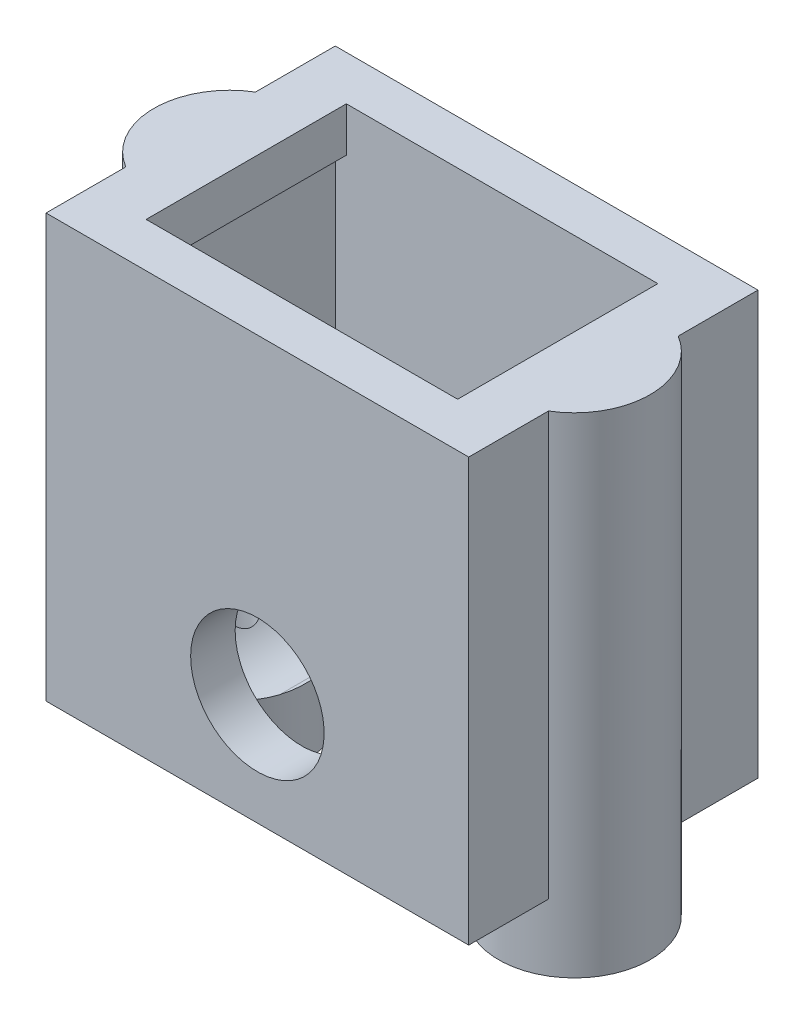
SolidWorks part; units mm, degrees
ref_plane "Plano frontal" through (0, 0, 0) normal (0, 0, 1) x (1, 0, 0)
ref_plane "Plano superior" through (0, 0, 0) normal (0, 1, 0) x (1, 0, 0)
ref_plane "Plano direito" through (0, 0, 0) normal (1, 0, 0) x (0, 0, -1)
sketch "Esboço1" plane through (0, 0, 0) normal (0, 1, 0) x (1, 0, 0)
  line L1 (-7.5, -4.5) -> (7.5, -4.5)
  line L2 (-7.5, -4.5) -> (-7.5, 4.5)
  line L3 (-7.5, 4.5) -> (7.5, 4.5)
  line L4 (7.5, -4.5) -> (7.5, 4.5)
  line L5 (-7.5, -4.5) -> (7.5, 4.5) construction
  line L6 (-7.5, 4.5) -> (7.5, -4.5) construction
  line L7 (-9.5, -6.5) -> (9.5, -6.5)
  line L8 (-9.5, -6.5) -> (-9.5, 6.5)
  line L9 (-9.5, 6.5) -> (9.5, 6.5)
  line L10 (9.5, -6.5) -> (9.5, 6.5)
  line L11 (-9.5, -6.5) -> (9.5, 6.5) construction
  line L12 (-9.5, 6.5) -> (9.5, -6.5) construction
  point P0 (0, 0)
  point P6 (0, 0)
  dimension "D1" = 15
  dimension "D2" = 9
  dimension "D3" = 2
  dimension "D4" = 2
extrude "Ressalto-extrusão1" add sketch "Esboço1" along normal blind 17
sketch "Esboço2" plane through (0, 0, 0) normal (0, -1, 0) x (1, 0, 0)
  line L0 (7.75, 0) -> (-7.75, 0) construction
  circle A0 centre (7.75, 0) radius 3.4
  circle A1 centre (-7.75, 0) radius 3.4
  circle A2 centre (-7.75, 0) radius 1
  circle A3 centre (7.75, 0) radius 1
  point P4 (0, 0)
  dimension "D2" = 6.8
  dimension "D3" = 6.8
  dimension "D4" = 2
  dimension "D5" = 2
  dimension "D1" = 15.5
extrude "Ressalto-extrusão2" add sketch "Esboço2" along normal blind 3
fillet "Filete1" radius 3 4 edges at (-7.5, 0, 2.1795) (-7.5, 0, -2.1795) (7.5, 0, -2.1795) (7.5, 0, 2.1795)
sketch "Esboço3" plane through (0, 0, 0) normal (0, 1, 0) x (1, 0, 0)
  line L1 (-9.5, -2.915) -> (-9.5, 2.915)
  line L2 (-9.5, -2.915) -> (-9.5, 2.915)
  line L3 (9.5, 2.915) -> (9.5, -2.915)
  line L4 (9.5, 2.915) -> (9.5, -2.915)
  arc A1 (-9.5, 2.915) -> (-9.5, -2.915) centre (-7.75, 0) ccw
  arc A2 (-9.5, 2.915) -> (-9.5, -2.915) centre (-7.75, 0) ccw
  arc A3 (9.5, -2.915) -> (9.5, 2.915) centre (7.75, 0) ccw
  arc A4 (9.5, -2.915) -> (9.5, 2.915) centre (7.75, 0) ccw
  dimension "D1" = 0
  dimension "D2" = 0
extrude "Ressalto-extrusão3" add sketch "Esboço3" along normal blind 19
sketch "Esboço5" plane through (0, 17, 0) normal (0, 1, 0) x (1, 0, 0)
  line L0 (7.5, 4.5) -> (-7.5, 4.5) construction
  line L1 (7, -4.5) -> (-7, -4.5)
  line L2 (7, -4.5) -> (7, 4.5)
  line L3 (7, 4.5) -> (-7, 4.5)
  line L4 (-7, -4.5) -> (-7, 4.5)
  line L5 (7, -4.5) -> (-7, 4.5) construction
  line L6 (7, 4.5) -> (-7, -4.5) construction
  line L7 (9.5, -6.5) -> (9.5, -2.915) construction
  line L8 (9.5, 6.5) -> (-9.5, 6.5) construction
  line L9 (-9.5, 6.5) -> (-9.5, 2.915) construction
  line L10 (-9.5, -2.915) -> (-9.5, -6.5) construction
  line L11 (-9.5, -6.5) -> (9.5, -6.5) construction
  line L12 (9.5, 2.915) -> (9.5, 6.5) construction
  line L13 (9.5, -6.5) -> (9.5, -2.915)
  line L14 (9.5, 2.915) -> (9.5, 6.5)
  line L15 (-9.5, -6.5) -> (9.5, -6.5)
  line L16 (-9.5, -2.915) -> (-9.5, -6.5)
  line L17 (-9.5, 6.5) -> (-9.5, 2.915)
  line L18 (9.5, 6.5) -> (-9.5, 6.5)
  line L20 (-3, -6.5) -> (3, -6.5)
  line L21 (-3, -4.5) -> (-3, 4.5)
  line L22 (-3, 6.5) -> (3, 6.5)
  line L23 (3, -4.5) -> (3, 4.5)
  line L24 (-2.0769, -4.5) -> (2.0769, 4.5) construction
  line L25 (-2.0769, 4.5) -> (2.0769, -4.5) construction
  line L26 (-9.5, -2.915) -> (9.5, -2.915)
  line L27 (-9.5, -2.915) -> (-9.5, 2.915)
  line L28 (-9.5, 2.915) -> (9.5, 2.915)
  line L29 (9.5, -2.915) -> (9.5, 2.915)
  line L30 (-9.5, -2.915) -> (9.5, 2.915) construction
  line L31 (-9.5, 2.915) -> (9.5, -2.915) construction
  arc A0 (-9.5, 2.915) -> (-9.5, -2.915) centre (-7.75, 0) ccw construction
  arc A1 (9.5, -2.915) -> (9.5, 2.915) centre (7.75, 0) ccw construction
  arc A2 (9.5, -2.915) -> (9.5, 2.915) centre (7.75, 0) ccw
  arc A3 (-9.5, 2.915) -> (-9.5, -2.915) centre (-7.75, 0) ccw
  point P0 (0, 0)
  point P10 (0, 0)
  point P31 (0, 0)
  line M3 (9.5, -6.5) -> (9.5, -2.915)
  line M5 (9.5, 2.915) -> (9.5, 6.5)
  line M6 (9.5, 6.5) -> (-9.5, 6.5)
  line M7 (-9.5, 6.5) -> (-9.5, 2.915)
  line M9 (-9.5, -2.915) -> (-9.5, -6.5)
  line M10 (-9.5, -6.5) -> (9.5, -6.5)
  line M11 (7.5, 4.5) -> (7.5, -4.5)
  line M12 (7.5, -4.5) -> (-7.5, -4.5)
  line M13 (-7.5, -4.5) -> (-7.5, 4.5)
  line M14 (-7.5, 4.5) -> (7.5, 4.5)
  dimension "D1" = 14
  dimension "D2" = 6
sketch "Esboço6" plane through (0, 0, -6.5) normal (0, 0, -1) x (-1, 0, 0)
  line L1 (-9.5, 0) -> (0, 0)
  line L2 (-9.5, 0) -> (-9.5, 5)
  line L3 (-9.5, 5) -> (0, 5)
  line L4 (0, 0) -> (0, 5)
  circle A0 centre (0, 5) radius 3
  dimension "D2" = 6
  dimension "D1" = 5
extrude "Corte-extrusão1" cut sketch "Esboço6" against normal through all contours L4 A0 L3 | L3 A0 L4 region at (1.2732, 3.7268, -6.5) region at (-0.4244, 5.4244, -6.5)
extrude "Ressalto-extrusão6" add sketch "Esboço5" along normal blind 2 contours L26 L15 L1 M9 M10 M3 M11 M12 M13 | L26 L2 M12 M11 | L2 L28 M11 M14 | L28 L3 L18 M7 M13 M14 M11 M5 M6 | L26 L4 M13 M12 | L28 L4 M13 M14 | L26 L29 L28 M11 | L28 L27 L26 M13 | L28 L26 L4 M13 | L28 L2 L26 M11 region at (0, 17, 5.2437) region at (7.25, 17, 3.7075) region at (7.25, 17, 0) region at (7.25, 17, -3.7075) region at (8.5, 17, 0) region at (-7.25, 17, 3.7075) region at (0, 17, -5.2437) region at (-7.25, 17, 0) region at (-7.25, 17, -3.7075) region at (-8.5, 17, 0)
sketch "Esboço7" plane through (0, -3, 0) normal (0, -1, 0) x (1, 0, 0)
  circle A0 centre (-7.75, 0) radius 1 construction
  circle A1 centre (7.75, 0) radius 1 construction
  circle A2 centre (-7.75, 0) radius 1
  circle A3 centre (7.75, 0) radius 1
extrude "Corte-extrusão2" cut sketch "Esboço7" against normal blind 6
